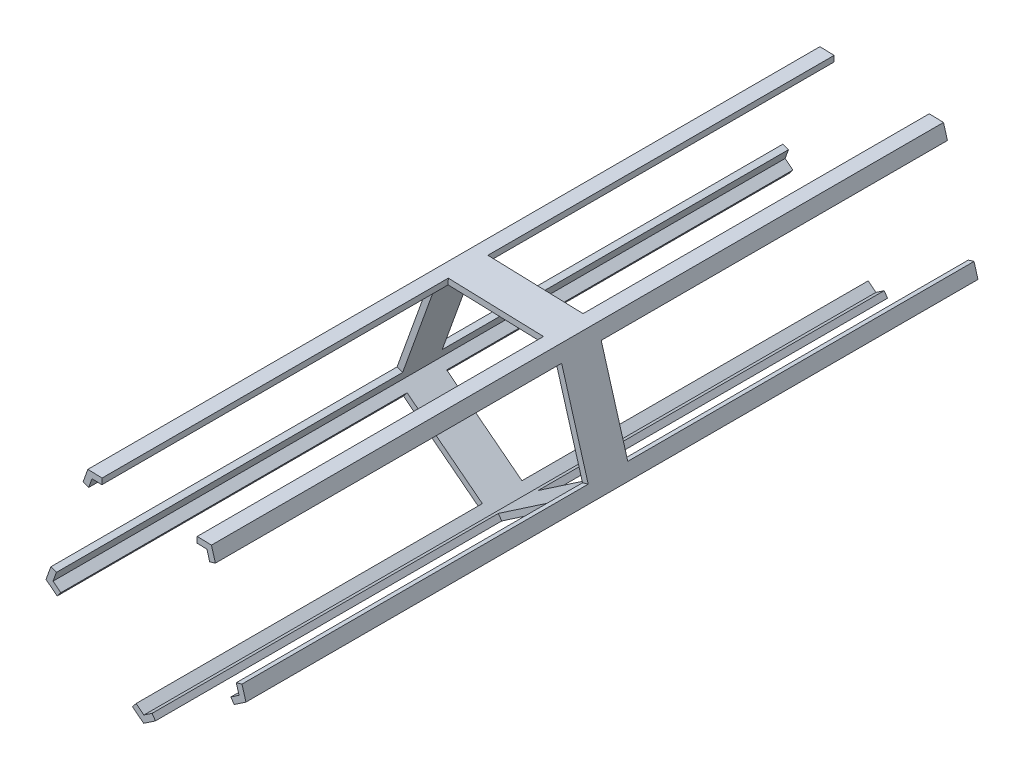
SolidWorks part; units mm, degrees
ref_plane "Front Plane" through (0, 0, 0) normal (0, 0, 1) x (1, 0, 0)
ref_plane "Top Plane" through (0, 0, 0) normal (0, 1, 0) x (1, 0, 0)
ref_plane "Right Plane" through (0, 0, 0) normal (1, 0, 0) x (0, 0, -1)
sketch "Sketch3" plane through (0, 0, 0) normal (0, 0, 1) x (1, 0, 0)
  line L0 (0, 0) -> (16.2851, 21.0012) construction
  line L1 (15.1489, 19.536) -> (-13.8986, 20.4445)
  line L2 (-13.8986, 20.4445) -> (-23.7387, -6.9006)
  line L3 (-23.7387, -6.9006) -> (-0.7728, -24.7093)
  line L4 (-0.7728, -24.7093) -> (23.2611, -8.3705)
  line L5 (-0.8307, -26.5625) -> (25.0057, -8.9983)
  line L6 (25.0057, -8.9983) -> (16.2851, 21.0012)
  line L7 (16.2851, 21.0012) -> (-14.941, 21.9778)
  line L8 (-14.941, 21.9778) -> (-25.5191, -7.4182)
  line L9 (-25.5191, -7.4182) -> (-0.8307, -26.5625)
  line L10 (-0.8307, -26.5625) -> (25.0057, -8.9983)
  line L11 (25.0057, -8.9983) -> (16.2851, 21.0012)
  line L12 (16.2851, 21.0012) -> (-14.941, 21.9778)
  line L13 (-14.941, 21.9778) -> (-25.5191, -7.4182)
  line L14 (-25.5191, -7.4182) -> (-0.8307, -26.5625)
  line L15 (23.2611, -8.3705) -> (15.1489, 19.536)
  circle A0 centre (0, 0) radius 20 construction
  point P4 (0, 0)
  dimension "D2" = 40
  dimension "D1" = 0
extrude "Boss-Extrude2" add sketch "Sketch3" along normal blind 185
ref_plane "Plane1" through (0, 0, 92.5) normal (0, 0, 1) x (1, 0, 0)
sketch "Sketch4" plane through (0, 0, 0) normal (0, 0, -1) x (-1, 0, 0)
  line L0 (14.745, 18.0921) -> (16.1564, 18.6)
  line L1 (13.8986, 20.4445) -> (23.7387, -6.9006) construction
  line L2 (14.941, 21.9778) -> (25.5191, -7.4182) construction
  line L3 (24.3036, -4.0404) -> (22.8922, -4.5483)
  line L4 (22.8922, -4.5483) -> (14.745, 18.0921)
  line L5 (24.3036, -4.0404) -> (16.1564, 18.6)
  dimension "D1" = 2.5
  dimension "D2" = 2.5
extrude "Cut-Extrude1" cut sketch "Sketch4" against normal offset from surface (87.5 mm away) 5 up to plane "Plane1"
ref_point "Point1"
ref_axis "Axis1" through (0, 0, 185) along (0, 0, 1)
pattern_circular "CirPattern1" count 5 over 360 about axis through (0, 0, 185) along (0, 0, 1) of "Cut-Extrude1"
mirror "Mirror1" about plane through (0, 0, 92.5) normal (0, 0, 1) of "CirPattern1"
